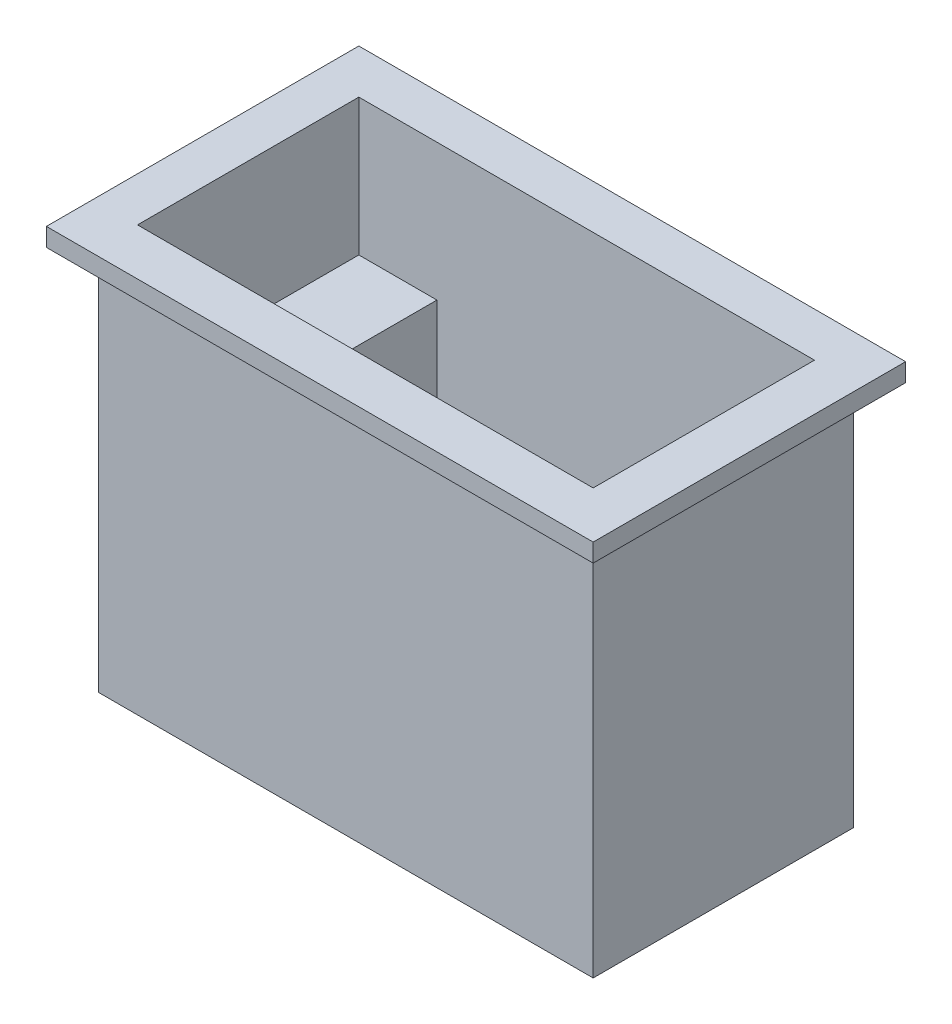
SolidWorks part; units mm, degrees
ref_plane "Front Plane" through (0, 0, 0) normal (0, 0, 1) x (1, 0, 0)
ref_plane "Top Plane" through (0, 0, 0) normal (0, 1, 0) x (1, 0, 0)
ref_plane "Right Plane" through (0, 0, 0) normal (1, 0, 0) x (0, 0, -1)
sketch "Sketch1" plane through (0, 0, 0) normal (0, 1, 0) x (1, 0, 0)
  line L1 (-10.4, 5.9429) -> (27.6, 5.9429)
  line L2 (-10.4, 5.9429) -> (-10.4, -14.0571)
  line L3 (-10.4, -14.0571) -> (27.6, -14.0571)
  line L4 (27.6, 5.9429) -> (27.6, -14.0571)
  dimension "D1" = 38
  dimension "D2" = 20
extrude "Boss-Extrude1" add sketch "Sketch1" along normal blind 31
sketch "Sketch2" plane through (0, 31, 0) normal (0, 1, 0) x (1, 0, 0)
  line L0 (27.6, 5.9429) -> (-10.4, 5.9429) construction
  line L1 (-9, 4.5429) -> (26, 4.5429)
  line L2 (-9, 4.5429) -> (-9, -12.4571)
  line L3 (-9, -12.4571) -> (26, -12.4571)
  line L4 (26, 4.5429) -> (26, -12.4571)
  line L5 (-10.4, 5.9429) -> (-10.4, -14.0571) construction
  dimension "D1" = 35
  dimension "D2" = 17
  dimension "D3" = 1.4
  dimension "D4" = 1.4
extrude "Cut-Extrude1" cut sketch "Sketch2" against normal blind 28
sketch "Sketch3" plane through (0, 3, 0) normal (0, 1, 0) x (1, 0, 0)
  line L0 (-9, -12.4571) -> (26, -12.4571) construction
  line L1 (-9, 4.5429) -> (-3, 4.5429)
  line L2 (-9, 4.5429) -> (-9, -12.4571)
  line L3 (-9, -12.4571) -> (-3, -12.4571)
  line L4 (-3, 4.5429) -> (-3, -12.4571)
  line L5 (26, 4.5429) -> (-9, 4.5429) construction
  line L6 (20, 4.5429) -> (26, 4.5429)
  line L7 (20, 4.5429) -> (20, -12.4571)
  line L8 (20, -12.4571) -> (26, -12.4571)
  line L9 (26, 4.5429) -> (26, -12.4571)
  dimension "D1" = 6
  dimension "D2" = 6
extrude "Boss-Extrude2" add sketch "Sketch3" along normal blind 17.5
sketch "Sketch4" plane through (0, 31, 0) normal (0, 1, 0) x (1, 0, 0)
  line L1 (-10.4, 5.9429) -> (27.6, 5.9429)
  line L2 (-10.4, 5.9429) -> (-10.4, -14.0571)
  line L3 (-10.4, -14.0571) -> (27.6, -14.0571)
  line L4 (27.6, 5.9429) -> (27.6, -14.0571)
extrude "Extrude-Thin2" add sketch "Sketch4" against normal blind 1.4 thin thin type one direction wall 2
sketch "Sketch5" plane through (0, 20.5, 0) normal (0, 1, 0) x (1, 0, 0)
  line L0 (-3, -12.4571) -> (-3, 4.5429) construction
  circle A0 centre (-5.5, -3.8921) radius 1
  dimension "D1" = 2
  dimension "D2" = 2.5
extrude "Cut-Extrude2" cut sketch "Sketch5" against normal blind 3
sketch "Sketch6" plane through (0, 20.5, 0) normal (0, 1, 0) x (1, 0, 0)
  circle A0 centre (22.9531, -4.1157) radius 1
  dimension "D1" = 2
extrude "Cut-Extrude3" cut sketch "Sketch6" against normal blind 3
sketch "Sketch7" plane through (-3, 0, 0) normal (1, 0, 0) x (0, 0, -1)
  line L0 (5.9429, 29.6) -> (5.9429, 0) construction
  line L1 (0.9429, 4.0414) -> (-8.4571, 4.0414)
  line L2 (0.9429, 4.0414) -> (0.9429, 8.5414)
  line L3 (0.9429, 8.5414) -> (-8.4571, 8.5414)
  line L4 (-8.4571, 4.0414) -> (-8.4571, 8.5414)
  point P4 (0.9429, 6.2914)
  dimension "D1" = 9.4
  dimension "D2" = 4.5
  dimension "D3" = 5
extrude "Cut-Extrude4" cut sketch "Sketch7" against normal blind 10
sketch "Sketch8" plane through (0, 3, 0) normal (0, 1, 0) x (1, 0, 0)
  line L1 (-1.4079, -8.7279) -> (18.5921, -8.7279)
  line L2 (-1.4079, -8.7279) -> (-1.4079, 1.2721)
  line L3 (-1.4079, 1.2721) -> (18.5921, 1.2721)
  line L4 (18.5921, -8.7279) -> (18.5921, 1.2721)
  dimension "D1" = 10
  dimension "D2" = 20
extrude "Cut-Extrude5" cut sketch "Sketch8" against normal blind 1.5
sketch "Sketch9" plane through (0, 1.5, 0) normal (0, 1, 0) x (1, 0, 0)
  circle A0 centre (8.8083, -3.6349) radius 3.7
  circle A3 centre (1.6083, -3.6349) radius 1
  circle A4 centre (16.0083, -3.6349) radius 1
  dimension "D1" = 7.4
  dimension "D2" = 3.5
  dimension "D5" = 2
  dimension "D4" = 2
  dimension "D3" = 3.5
extrude "Cut-Extrude6" cut sketch "Sketch9" against normal blind 1.7
fillet "Fillet1" radius 4 4 edges at (18.5921, 2.25, -1.2721) (18.5921, 2.25, 8.7279) (-1.4079, 2.25, -1.2721) (-1.4079, 2.25, 8.7279)
